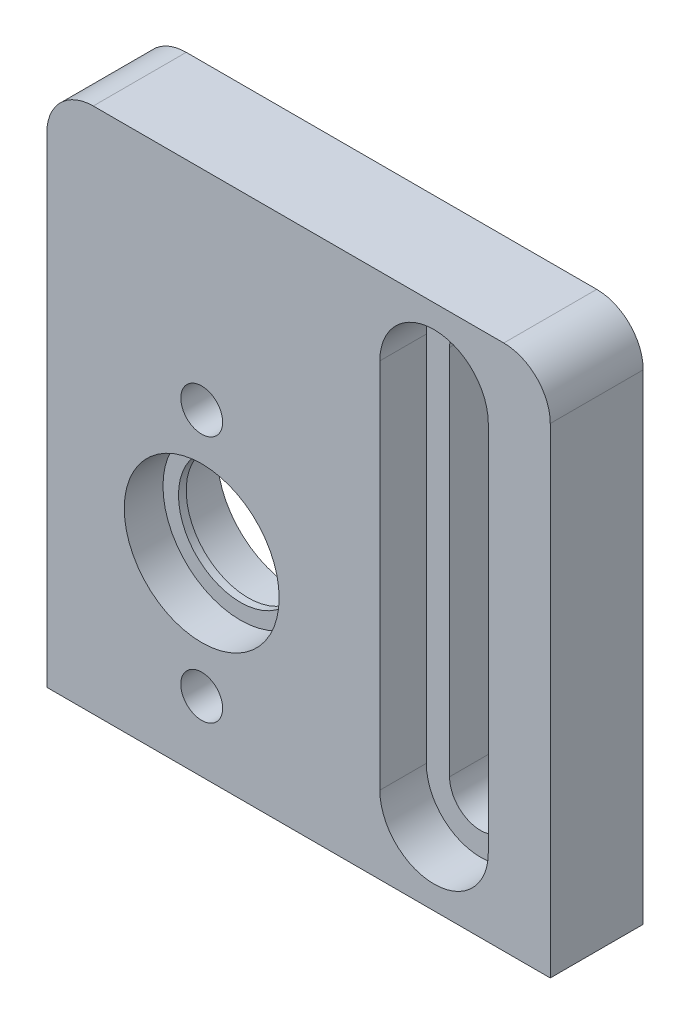
SolidWorks part; units mm, degrees
ref_plane "Ebene vorne" through (0, 0, 0) normal (0, 0, 1) x (1, 0, 0)
ref_plane "Ebene oben" through (0, 0, 0) normal (0, 1, 0) x (1, 0, 0)
ref_plane "Ebene rechts" through (0, 0, 0) normal (1, 0, 0) x (0, 0, -1)
sketch "Skizze1" plane through (0, 0, 0) normal (0, 0, 1) x (1, 0, 0)
  line L0 (20.5, 0) -> (20.5, -15.5) construction
  line L1 (-32.5, 18.5) -> (32.5, 18.5)
  line L2 (-32.5, 18.5) -> (-32.5, -15.5)
  line L3 (-32.5, -15.5) -> (32.5, -15.5)
  line L4 (32.5, 18.5) -> (32.5, -15.5)
  line L5 (-32.5, 0) -> (32.5, 0) construction
  line L6 (-22.5, -3) -> (-22.5, -15.5) construction
  circle A0 centre (20.5, 0) radius 10.5
  circle A1 centre (20.5, 0) radius 9
  circle A2 centre (-22.5, -3) radius 4
  circle A3 centre (-22.5, -3) radius 5
  circle A4 centre (-22.5, -3) radius 8 construction
  dimension "D3" = 21
  dimension "D4" = 18
  dimension "D7" = 10
  dimension "D8" = 8
  dimension "D9" = 16
  dimension "D1" = 65
  dimension "D2" = 34
  dimension "D5" = 15.5
  dimension "D6" = 12
  dimension "D10" = 10
  dimension "D11" = 12.5
  dimension "D12" = 21.5
extrude "Aufsatz-Linear austragen1" add sketch "Skizze1" against normal mid plane 6 contours L1 L4 L3 L2 | A1 | A2
extrude "Schnitt-Linear austragen1" cut sketch "Skizze1<3>" against normal blind 5 from surface contours A0 starting at face at (-18.5, -3, 3)
sketch "Skizze1<3>" plane through (0, 0, 0) normal (0, 0, 1) x (1, 0, 0) same geometry as "Skizze1"
extrude "Schnitt-Linear austragen2" cut sketch "Skizze1<4>" against normal blind 3 from surface contours A3 starting at face at (31, 0, 3)
sketch "Skizze1<4>" plane through (0, 0, 0) normal (0, 0, 1) x (1, 0, 0) same geometry as "Skizze1"
sketch "Skizze11" plane through (0, 0, -3) normal (0, 0, -1) x (-1, 0, 0)
  line L0 (7.5, 13.5) -> (7.5, -10.5) construction
  line L1 (9.5, 13.5) -> (9.5, -10.5)
  line L2 (5.5, 13.5) -> (5.5, -10.5)
  line L3 (32.5, 18.5) -> (-32.5, 18.5) construction
  line L4 (32.5, 18.5) -> (32.5, -15.5) construction
  line L5 (32.5, -15.5) -> (-32.5, -15.5) construction
  line L6 (7.5, 13.5) -> (7.5, -10.5) construction
  line L7 (11, 13.5) -> (11, -10.5)
  line L8 (4, 13.5) -> (4, -10.5)
  arc A0 (9.5, 13.5) -> (5.5, 13.5) centre (7.5, 13.5) ccw
  arc A1 (5.5, -10.5) -> (9.5, -10.5) centre (7.5, -10.5) ccw
  arc A2 (11, 13.5) -> (4, 13.5) centre (7.5, 13.5) ccw
  arc A3 (4, -10.5) -> (11, -10.5) centre (7.5, -10.5) ccw
  point P2 (7.5, 1.5)
  point P15 (7.5, 1.5)
  dimension "D1" = 4
  dimension "D2" = 5
  dimension "D3" = 5
  dimension "D4" = 25
  dimension "D5" = 7
extrude "Schnitt-Linear austragen4" cut sketch "Skizze11" against normal through all contours L2 A1 L1 A0
extrude "Schnitt-Linear austragen5" cut sketch "Skizze11<4>" against normal blind 3 contours L8 A3 L7 A2
sketch "Skizze11<4>" plane through (0, 0, -3) normal (0, 0, -1) x (-1, 0, 0) same geometry as "Skizze11"
fillet "Verrundung1" radius 3 2 edges at (32.5, 18.5, 0) (-32.5, 18.5, 0)
hole_wizard "M3 Gewindebohrung1" positions "Skizze4" profile "Skizze5" tap size "M3" standard "DIN"
sketch "Skizze4" plane through (-30, -15.5, -6.25) normal (0, -1, 0) x (-1, 0, 0)
  line L2 (-30, -6.75) -> (-30, -6.25) construction
  line L4 (-56.5, -6.75) -> (-44.5, -6.75) construction
  line L5 (-44.5, -6.75) -> (-13.5, -6.75) construction
  line L6 (-13.5, -6.75) -> (-1.5, -6.75) construction
  line L8 (2.5, -3.25) -> (-62.5, -3.25) construction
  line L10 (-50.5, -6.75) -> (-50.5, -3.25) construction
  line L12 (-41.5, -3.25) -> (-59.5, -3.25) construction
  line L14 (-7.5, -6.75) -> (-7.5, -3.25) construction
  line L16 (-3.5, -3.25) -> (-11.5, -3.25) construction
  point P0 (-56.5, -6.75)
  point P2 (-1.5, -6.75)
  point P21 (-44.5, -6.75)
  point P23 (-13.5, -6.75)
  dimension "D1" = 12
  dimension "D2" = 3.5
sketch "Skizze5" plane through (26.5, -15.5, 0.5) normal (1, 0, 0) x (0, 0, -1)
  line L0 (0, 0) -> (0, 7.7511)
  line L1 (0, 7.7511) -> (1.25, 7)
  line L2 (1.25, 7) -> (1.25, 0)
  line L5 (1.25, 0) -> (0, 0)
  line L10 (0, 7.7511) -> (-1.25, 7) construction
  line L11 (0, -6.35) -> (0, 107.95) construction
  dimension "Bohrerdurchmesser" = 2.5
  dimension "Bohrungstiefe" = 7
  dimension "Spitzenwinkel" = 118
cosmetic thread "Bohrungsgewinde3" parameters "D1"=5, "D2"=3
cosmetic thread "Bohrungsgewinde4" parameters "D1"=5, "D2"=3
cosmetic thread "Bohrungsgewinde5" [suppressed] parameters "D1"=5, "D2"=3
cosmetic thread "Bohrungsgewinde6" [suppressed] parameters "D1"=5, "D2"=3
hole_wizard "M3 Gewindebohrung2" positions "Skizze13" profile "Skizze12" tap size "M3" standard "DIN"
sketch "Skizze13" plane through (0, 18.5, 0) normal (0, 1, 0) x (1, 0, 0)
  line L3 (0, 0) -> (20.5, 0) construction
  line L5 (32.5, 3) -> (32.5, -3) construction
  point P0 (20.5, 0)
  dimension "D1" = 12
sketch "Skizze12" plane through (20.5, 18.5, 0) normal (1, 0, 0) x (0, 0, 1)
  line L0 (0, 0) -> (0, 8.2511)
  line L1 (0, 8.2511) -> (1.25, 7.5)
  line L2 (1.25, 7.5) -> (1.25, 0)
  line L5 (1.25, 0) -> (0, 0)
  line L10 (0, 8.2511) -> (-1.25, 7.5) construction
  line L11 (0, -6.35) -> (0, 107.95) construction
  dimension "Bohrerdurchmesser" = 2.5
  dimension "Bohrungstiefe" = 7.5
  dimension "Spitzenwinkel" = 118
cosmetic thread "Bohrungsgewinde7" parameters "D1"=5, "D2"=3
mirror "Spiegeln1" about plane through (0, 0, 3) normal (0, 0, 1) of bodies 117 104
delete or keep bodies "Körper-Löschen1" type delete bodies bodies 117
sketch "Skizze6" plane through (0, 0, 3) normal (0, 0, -1) x (-1, 0, 0)
  line L1 (-32.5, -15.5) -> (-8.5, -15.5)
  line L2 (-32.5, -15.5) -> (-32.5, 18.5)
  line L3 (-32.5, 18.5) -> (-8.5, 18.5)
  line L4 (-8.5, -15.5) -> (-8.5, 18.5)
  line L6 (32.5, -15.5) -> (0, -15.5)
  line L7 (32.5, -15.5) -> (32.5, 18.5)
  line L8 (32.5, 18.5) -> (0, 18.5)
  line L9 (0, -15.5) -> (0, 18.5)
  line L10 (-20.5, -15.5) -> (-20.5, 0) construction
  line L12 (29.5, 18.5) -> (-29.5, 18.5) construction
  circle A0 centre (-20.5, 0) radius 10.5 construction
extrude "Nur Abtrieb" [suppressed] cut sketch "Skizze6" against normal through all flip side to cut
fillet "Verrundung2" [suppressed] radius 3
extrude "Nur Antrieb" cut sketch "Skizze6<3>" against normal through all flip side to cut contours L9 L8 L7 L6
sketch "Skizze6<3>" plane through (0, 0, 3) normal (0, 0, -1) x (-1, 0, 0) same geometry as "Skizze6"
fillet "Verrundung3" radius 3 1 edges at (0, 18.5, 6)
sketch "Skizze7" plane through (0, 0, 9) normal (0, 0, -1) x (-1, 0, 0)
  circle A0 centre (22.5, -3) radius 5
  dimension "D1" = 10
extrude "Schnitt-Linear austragen3" cut sketch "Skizze7" along normal blind 2.5
hole_wizard "Stirnsenkung für  M2.5 Zylinderschraube mit Schlitz/Kreuzschlitz1" positions "Skizze9" profile "Skizze10" counterbore size "M2.5" standard "DIN" end condition through all
sketch "Skizze9" plane through (6.814, -2.6102, 3) normal (0, 0, 1) x (1, 0, 0)
  line L1 (-29.314, 7.6102) -> (-29.314, -0.3898) construction
  line L2 (-29.314, -0.3898) -> (-29.314, -8.3898) construction
  circle A0 centre (-29.314, -0.3898) radius 8 construction
  point P0 (-29.314, 7.6102)
  point P4 (-29.314, -8.3898)
sketch "Skizze10" plane through (-22.5, 5, 3) normal (1, 0, 0) x (0, 1, 0)
  line L0 (0, 0) -> (0, 6)
  line L1 (0, 6) -> (1.35, 6)
  line L3 (1.35, 6) -> (1.35, 1.8)
  line L4 (1.35, 1.8) -> (2.75, 1.8)
  line L5 (2.75, 1.8) -> (2.75, 0)
  line L7 (2.75, 0) -> (0, 0)
  line L11 (0, -6.35) -> (0, 107.95) construction
  dimension "Bohrerdurchmesser" = 2.7
  dimension "Bohrungstiefe" = 6
  dimension "Senkdurchmesser2" = 5.5
  dimension "Senktiefe2" = 1.8
